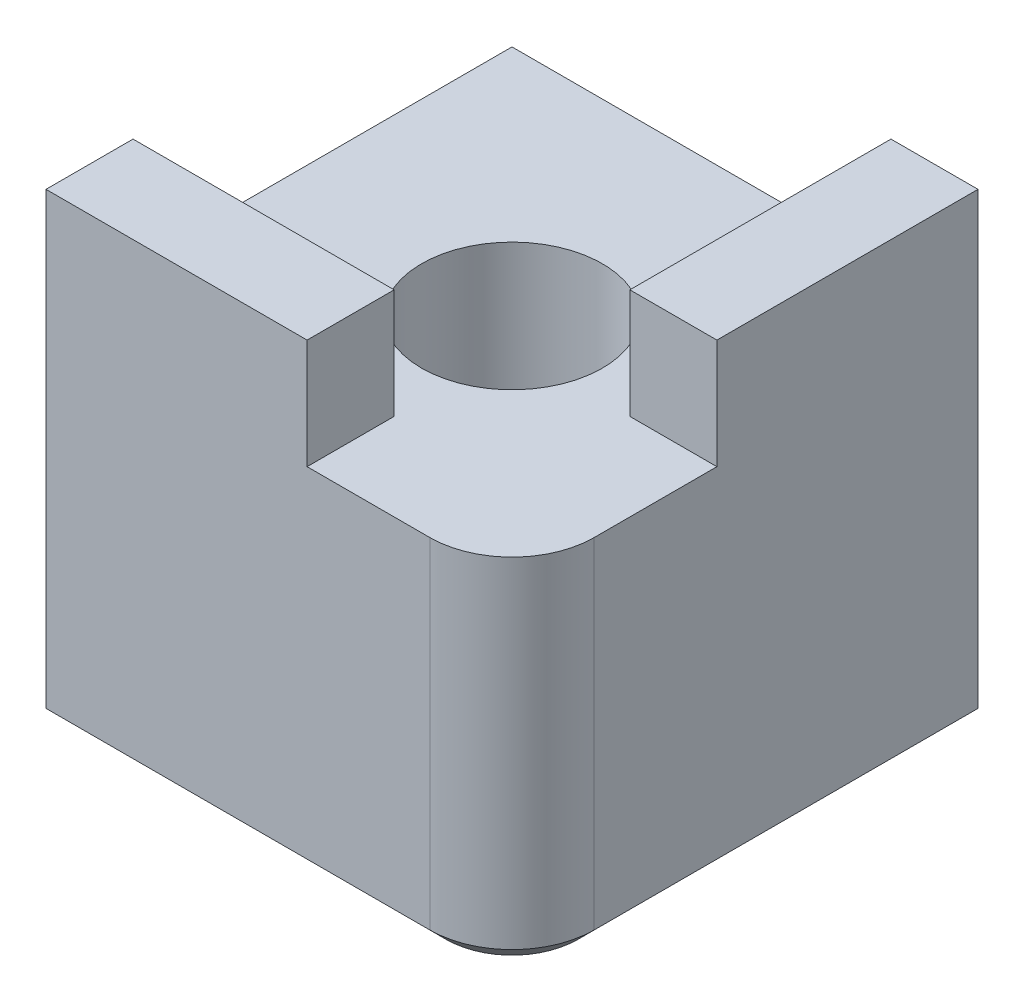
SolidWorks part; units mm, degrees
material "6061-T6 (SS)"
ref_plane "Front Plane" through (0, 0, 0) normal (0, 0, 1) x (1, 0, 0)
ref_plane "Top Plane" through (0, 0, 0) normal (0, 1, 0) x (1, 0, 0)
ref_plane "Right Plane" through (0, 0, 0) normal (1, 0, 0) x (0, 0, -1)
sketch "Base" plane through (0, 0, 0) normal (0, 1, 0) x (1, 0, 0)
  line L1 (-4.25, -4.25) -> (4.25, -4.25)
  line L2 (-4.25, -4.25) -> (-4.25, 4.25)
  line L3 (-4.25, 4.25) -> (4.25, 4.25)
  line L4 (4.25, -4.25) -> (4.25, 4.25)
  line L5 (-4.25, -4.25) -> (4.25, 4.25) construction
  line L6 (-4.25, 4.25) -> (4.25, -4.25) construction
  point P0 (0, 0)
  dimension "D1" = 8.5
  dimension "D2" = 8.5
extrude "Boss-Extrude1" add sketch "Base" against normal blind 8
sketch "Cutout" plane through (0, 0, 0) normal (0, 1, 0) x (1, 0, 0)
  line L1 (-4.25, 4.25) -> (2.75, 4.25)
  line L2 (-4.25, 4.25) -> (-4.25, -2.75)
  line L3 (-4.25, -2.75) -> (2.75, -2.75)
  line L4 (2.75, 4.25) -> (2.75, -2.75)
  line L5 (2.75, -2.75) -> (-4.25, 4.25) construction
  line L6 (2.75, 4.25) -> (-4.25, -2.75) construction
  point P5 (-0.75, 0.75)
  dimension "D1" = 7
  dimension "D2" = 7
extrude "Cut-Extrude1" cut sketch "Cutout" against normal blind 1.5
sketch "Sketch3" plane through (2.75, 0, 0) normal (-1, 0, 0) x (0, 0, 1)
  line L0 (2.75, -1.5) -> (-4.25, -1.5) construction
  line L1 (-4.25, 0) -> (-2.75, 0)
  line L2 (-4.25, 0) -> (-4.25, -1.5)
  line L3 (-4.25, -1.5) -> (-2.75, -1.5)
  line L4 (-2.75, 0) -> (-2.75, -1.5)
  dimension "D1" = 1.5
extrude "Cut-Extrude2" cut sketch "Sketch3" against normal through all
ref_axis "Axis2" through (2.75, -1.5, 2.75) along (-0.7071, 0, -0.7071)
ref_plane "Plane1" through (0, 0, 0) normal (0.7071, 0, -0.7071) x (-0.7071, 0, -0.7071)
mirror "Mirror1" about plane through (0, 0, 0) normal (0.7071, 0, -0.7071) of "Cut-Extrude2"
fillet "Fillet3" radius 0.508 1 edges at (2.75, -0.75, 2.75)
fillet "Fillet4" radius 1.5 1 edges at (4.25, -4, 4.25)
hole_wizard "M4 Tapped Hole1" positions "Sketch12" profile "Sketch13" tap size "M4" standard "AS" end condition through all
sketch "Sketch12" plane through (0, -1.5, 0) normal (0, 1, 0) x (1, 0, 0)
  line L3 (4.25, -2.75) -> (4.25, 2.75) construction
  line L4 (-2.75, -4.25) -> (2.75, -4.25) construction
  point P0 (0, 0)
  dimension "D1" = 4.25
  dimension "D2" = 4.25
cosmetic thread "Hole Thread1" parameters "D2"=4
sketch "Sketch13" plane through (0, -1.5, 0) normal (1, 0, 0) x (0, 0, 1)
  line L0 (0, 0) -> (0, 6.5)
  line L1 (0, 6.5) -> (1.65, 6.5)
  line L2 (1.65, 6.5) -> (1.65, 0)
  line L5 (1.65, 0) -> (0, 0)
  line L11 (0, -6.35) -> (0, 107.95) construction
  dimension "Thru Tap Drill Dia." = 3.3
  dimension "Thru Tap Drill Depth" = 6.5
chamfer "Chamfer1" distance 0.3 angle 45 5 edges at (-4.25, -8, 0) (-0.75, -8, 4.25) (3.8107, -8, 3.8107) (4.25, -8, -0.75) (0, -8, -4.25)
sketch "Sketch14" plane through (0, 0, 0) normal (0, 1, 0) x (1, 0, 0)
  line L6 (-2.75, -4.25) -> (2.75, -4.25)
  line L7 (4.25, -2.75) -> (4.25, 2.75)
  line L8 (4.25, 2.75) -> (2.75, 2.75)
  line L9 (2.75, 2.75) -> (2.75, -2.242)
  line L10 (2.242, -2.75) -> (-2.75, -2.75)
  line L11 (-2.75, -2.75) -> (-2.75, -4.25)
  line L12 (-2.75, -4.25) -> (2.75, -4.25)
  line L13 (4.25, -2.75) -> (4.25, 2.75)
  line L14 (4.25, 2.75) -> (2.75, 2.75)
  line L15 (2.75, 2.75) -> (2.75, -2.242)
  line L16 (2.242, -2.75) -> (-2.75, -2.75)
  line L17 (-2.75, -2.75) -> (-2.75, -4.25)
  arc A2 (2.75, -4.25) -> (4.25, -2.75) centre (2.75, -2.75) ccw
  arc A3 (2.242, -2.75) -> (2.75, -2.242) centre (2.242, -2.242) ccw
  arc A4 (2.75, -4.25) -> (4.25, -2.75) centre (2.75, -2.75) ccw
  arc A5 (2.242, -2.75) -> (2.75, -2.242) centre (2.242, -2.242) ccw
  dimension "D1" = 0
extrude "Cut-Extrude3" cut sketch "Sketch14" against normal up to surface (1.5 mm away) up to face at (0, -1.5, 1.65)
sketch "Sketch15" plane through (0, -1.5, 0) normal (0, 1, 0) x (1, 0, 0)
  line L0 (0, 4.25) -> (0, 0) construction
  line L1 (4.25, 4.25) -> (-4.25, 4.25) construction
  line L2 (0, 0) -> (-4.25, 0) construction
  line L3 (-4.25, 4.25) -> (-4.25, -4.25) construction
  circle A0 centre (0, 3) radius 0.5
  circle A1 centre (-3, 0) radius 0.5
  dimension "D1" = 1
  dimension "D2" = 1.25
  dimension "D3" = 1.25
sketch "Sketch16" plane through (0, -1.5, 0) normal (0, 1, 0) x (1, 0, 0)
  line L1 (4.25, 4.25) -> (2.6625, 4.25)
  line L2 (4.25, 4.25) -> (4.25, -0.5125)
  line L3 (4.25, -0.5125) -> (2.6625, -0.5125)
  line L4 (2.6625, 4.25) -> (2.6625, -0.5125)
  line L5 (-4.25, -4.25) -> (0.5125, -4.25)
  line L6 (-4.25, -4.25) -> (-4.25, -2.6625)
  line L7 (-4.25, -2.6625) -> (0.5125, -2.6625)
  line L8 (0.5125, -4.25) -> (0.5125, -2.6625)
  dimension "D1" = 1.5875
  dimension "D2" = 4.7625
extrude "Boss-Extrude2" add sketch "Sketch16" along normal blind 2
